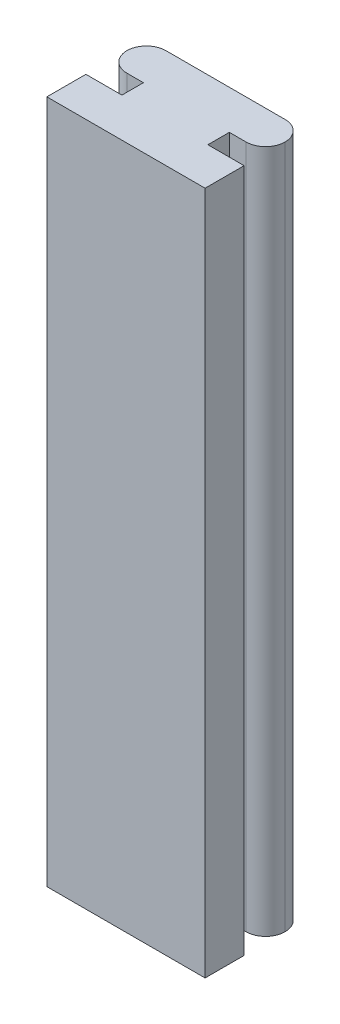
SolidWorks part; units mm, degrees
ref_plane "Front Plane" through (0, 0, 0) normal (0, 0, 1) x (1, 0, 0)
ref_plane "Top Plane" through (0, 0, 0) normal (0, 1, 0) x (1, 0, 0)
ref_plane "Right Plane" through (0, 0, 0) normal (1, 0, 0) x (0, 0, -1)
sketch "Sketch1" plane through (0, 0, 0) normal (0, 1, 0) x (1, 0, 0)
  line L1 (0, 0) -> (205.7636, 0)
  line L2 (0, 0) -> (0, -129.4551)
  line L3 (0, -129.4551) -> (205.7636, -129.4551)
  line L4 (205.7636, 0) -> (205.7636, -129.4551)
extrude "Boss-Extrude1" add sketch "Sketch1" along normal blind 889.508 contours L4 L1 L2 L3 | L2 L1 L4 L3 region at (102.8818, 0, 64.7275)
sketch "Sketch2" plane through (0, 889.508, 0) normal (0, 1, 0) x (1, 0, 0)
  line L1 (0, 0) -> (0, -129.4551) construction
  line L2 (0, -50.7596) -> (34.2281, -50.7596)
  line L3 (34.2281, -50.7596) -> (34.2281, -78.6955)
  line L4 (34.2281, -78.6955) -> (0, -78.6955)
  line L5 (0, -78.6955) -> (0, -50.7596)
extrude "Cut-Extrude1" cut sketch "Sketch2" against normal blind 1151.636 contours L2 L3 L4 L5
sketch "Sketch3" plane through (0, 889.508, 0) normal (0, 1, 0) x (1, 0, 0)
  line L0 (205.7636, -50.7596) -> (171.5355, -50.7596)
  line L1 (205.7636, 0) -> (205.7636, -129.4551) construction
  line L2 (171.5355, -50.7596) -> (171.5355, -78.6955)
  line L3 (171.5355, -78.6955) -> (205.7636, -78.6955)
  line L4 (205.7636, -78.6955) -> (205.7636, -50.7596)
extrude "Cut-Extrude2" cut sketch "Sketch3" against normal blind 1331.214 contours L4 L0 L2 L3
fillet "Fillet3" radius 25.4 1 edges at (0, 444.754, 0)
fillet "Fillet4" radius 25.4 1 edges at (205.7636, 444.754, 0)
fillet "Fillet5" radius 25.4 1 edges at (205.7636, 444.754, 50.7596)
fillet "Fillet7" radius 25.4 1 edges at (0, 444.754, 50.7596)
sketch "Sketch4" plane through (0, 889.508, 0) normal (0, 1, 0) x (1, 0, 0)
  line L0 (34.2281, -50.7596) -> (46.8783, -50.7596)
  line L1 (34.2281, -78.6955) -> (46.8783, -78.6955)
  line L2 (46.8783, -78.6955) -> (46.8783, -50.7596)
  line L3 (34.2281, -50.7596) -> (34.2281, -78.6955)
extrude "Boss-Extrude3" add sketch "Sketch4" against normal blind 874.268 contours L3 L1 L2 L0
sketch "Sketch5" plane through (0, 889.508, 0) normal (0, 1, 0) x (1, 0, 0)
  line L0 (34.2281, -50.7596) -> (46.8495, -50.7596)
  line L1 (46.8495, -50.7596) -> (46.8495, -78.6955)
  line L2 (46.8495, -78.6955) -> (34.2281, -78.6955)
  line L3 (34.2281, -78.6955) -> (34.2281, -50.7596)
extrude "Cut-Extrude5" cut sketch "Sketch5" against normal blind 1063.752 contours L3 L0 L1 L2
sketch "Sketch6" plane through (0, 889.508, 0) normal (0, 1, 0) x (1, 0, 0)
  line L0 (171.5355, -50.7596) -> (158.6218, -50.7596)
  line L1 (158.6218, -50.7596) -> (158.6218, -78.6955)
  line L2 (158.6218, -78.6955) -> (171.5355, -78.6955)
  line L3 (171.5355, -50.7596) -> (171.5355, -78.6955) construction
  line L4 (171.5355, -78.6955) -> (171.5355, -50.7596)
extrude "Cut-Extrude6" cut sketch "Sketch6" against normal blind 1244.346 contours L4 L0 L1 L2
sketch "Sketch7" plane through (46.8495, 0, 0) normal (-1, 0, 0) x (0, 0, 1)
  circle A0 centre (63.6837, 855.9143) radius 7.673
extrude "Cut-Extrude7" cut sketch "Sketch7" against normal blind 285.75
